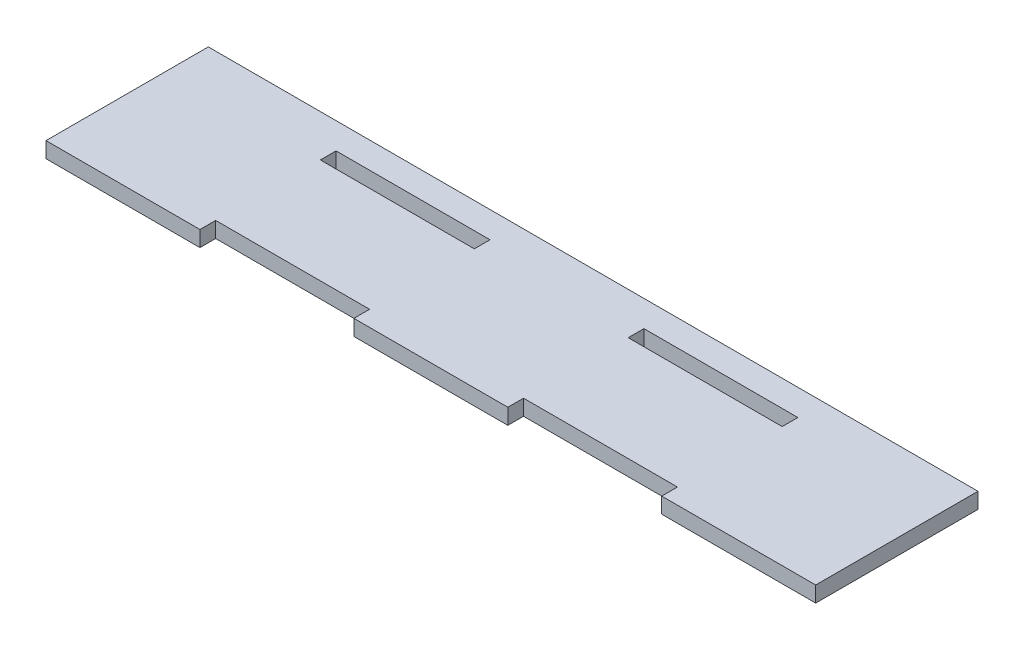
SolidWorks part; units mm, degrees
ref_plane "Front Plane" through (0, 0, 0) normal (0, 0, 1) x (1, 0, 0)
ref_plane "Top Plane" through (0, 0, 0) normal (0, 1, 0) x (1, 0, 0)
ref_plane "Right Plane" through (0, 0, 0) normal (1, 0, 0) x (0, 0, -1)
sketch "Sketch1" plane through (0, 0, 0) normal (0, 1, 0) x (1, 0, 0)
  line L0 (14.7, 7.5) -> (44.1, 7.5)
  line L1 (-73.5, 15.5) -> (73.5, 15.5)
  line L2 (-73.5, 15.5) -> (-73.5, -15.5)
  line L3 (-73.5, -15.5) -> (-44.1, -15.5)
  line L4 (73.5, 15.5) -> (73.5, -15.5)
  line L5 (-44.1, 10.5) -> (-14.7, 10.5)
  line L6 (-44.1, -12.5) -> (-14.7, -12.5)
  line L7 (-44.1, 7.5) -> (-14.7, 7.5)
  line L8 (14.7, 10.5) -> (44.1, 10.5)
  line L9 (-44.1, -12.5) -> (-44.1, -15.5)
  line L10 (-44.1, 10.5) -> (-44.1, 7.5)
  line L11 (-14.7, 10.5) -> (-14.7, 7.5)
  line L12 (14.7, 10.5) -> (14.7, 7.5)
  line L13 (44.1, 10.5) -> (44.1, 7.5)
  line L14 (-14.7, -12.5) -> (-14.7, -15.5)
  line L15 (14.7, -12.5) -> (14.7, -15.5)
  line L16 (44.1, -12.5) -> (44.1, -15.5)
  line L17 (-14.7, -15.5) -> (14.7, -15.5)
  line L18 (44.1, -15.5) -> (73.5, -15.5)
  line L19 (14.7, -12.5) -> (44.1, -12.5)
  point P0 (0, 0)
  dimension "D1" = 31
  dimension "D2" = 147
  dimension "D3" = 20
extrude "Boss-Extrude1" add sketch "Sketch1" along normal blind 3
